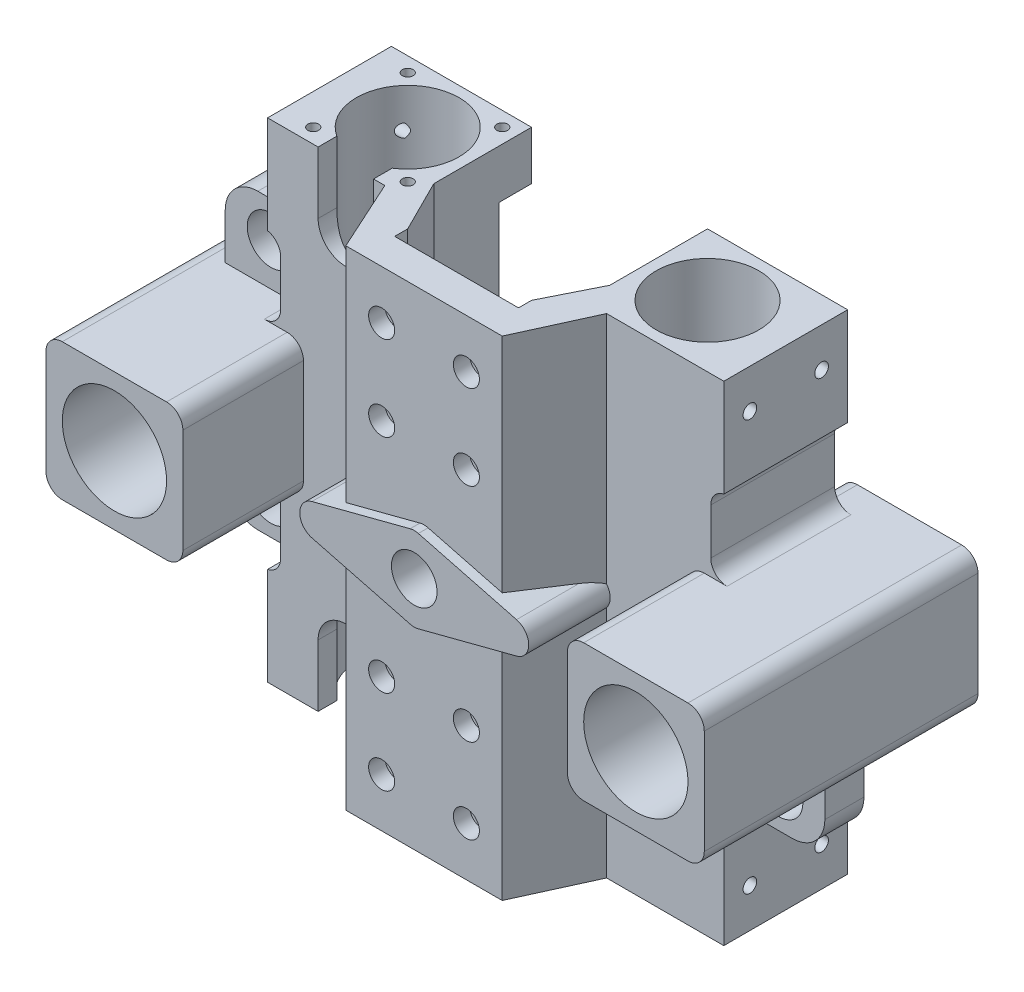
SolidWorks part; units mm, degrees
ref_plane "前视基准面" through (0, 0, 0) normal (0, 0, 1) x (1, 0, 0)
ref_plane "上视基准面" through (0, 0, 0) normal (0, 1, 0) x (1, 0, 0)
ref_plane "右视基准面" through (0, 0, 0) normal (1, 0, 0) x (0, 0, -1)
sketch "草图1" plane through (0, 0, 0) normal (0, 1, 0) x (1, 0, 0)
  line L0 (-70, 0) -> (-27, 0)
  line L1 (-27, 0) -> (-27, -30)
  line L2 (-27, -30) -> (-19, -46)
  line L3 (-19, -46) -> (-19, -50)
  line L4 (-19, -50) -> (19, -50)
  line L5 (0, 0) -> (0, -50.2692) construction
  line L6 (19, -46) -> (19, -50)
  line L7 (27, -30) -> (19, -46)
  line L8 (27, 0) -> (27, -30)
  line L9 (70, 0) -> (27, 0)
  line L10 (-70, 0) -> (-70, -38)
  line L11 (-70, -38) -> (-34.026, -38)
  line L12 (-34.026, -38) -> (-24, -60)
  line L13 (34.026, -38) -> (24, -60)
  line L14 (70, -38) -> (34.026, -38)
  line L15 (-24, -60) -> (24, -60)
  line L16 (70, 0) -> (70, -38)
  point P10 (0, -41.3877)
  dimension "D1" = 140
  dimension "D2" = 54
  dimension "D3" = 4
  dimension "D4" = 38
  dimension "D5" = 50
  dimension "D6" = 30
  dimension "D7" = 60
  dimension "D8" = 38
  dimension "D9" = 48
  dimension "D10" = 49
extrude "凸台-拉伸1" add sketch "草图1" along normal mid plane 150
sketch "草图2" plane through (0, 0, 60) normal (0, 0, 1) x (1, 0, 0)
  line L0 (-50, 0) -> (0, 13)
  line L1 (0, 13) -> (50, 0)
  line L2 (0, 0) -> (50, 0) construction
  line L3 (0, 0) -> (0, 26.231) construction
  line L4 (0, -13) -> (50, 0)
  line L5 (-50, 0) -> (0, -13)
  dimension "D1" = 26
  dimension "D2" = 100
extrude "凸台-拉伸2" add sketch "草图2" along normal blind 3 and the other way up to surface other way up to face at (0, 0, 50)
fillet "圆角1" radius 5 2 edges at (0, -13, 61.5) (0, 13, 61.5)
sketch "草图3" plane through (0, 0, 63) normal (0, 0, 1) x (1, 0, 0)
  circle A0 centre (0, 0) radius 7
  dimension "D1" = 14
extrude "切除-拉伸1" cut sketch "草图3" against normal through all
sketch "草图5" plane through (0, 0, 50) normal (0, 0, -1) x (-1, 0, 0)
  circle A0 centre (0, 0) radius 12.75
  dimension "D1" = 25.5
extrude "切除-拉伸2" cut sketch "草图5" against normal blind 3
hole_wizard "孔1" positions "草图7" profile "草图6" legacy end condition through all
sketch "草图7" plane through (0, 0, 60) normal (0, 0, 1) x (1, 0, 0)
  line L0 (0, 0) -> (0, 65.4079) construction
  line L2 (0, 0) -> (51.5584, 0) construction
  point P0 (-13, 34)
  point P1 (-13, 60)
  point P13 (13, 60)
  point P14 (13, 34)
  point P15 (13, -34)
  point P16 (13, -60)
  point P17 (-13, -60)
  point P18 (-13, -34)
  dimension "D1" = 68
  dimension "D2" = 26
  dimension "D3" = 26
sketch "草图6" plane through (-13, 34, 60) normal (1, 0, 0) x (0, -1, 0)
  line L0 (0, 0) -> (0, 60)
  line L1 (0, 60) -> (2.25, 60)
  line L2 (2.25, 60) -> (2.25, 5)
  line L3 (2.25, 5) -> (4, 5)
  line L4 (4, 5) -> (4, 0)
  line L5 (4, 0) -> (0, 0)
  line L6 (0, 110) -> (0, -10) construction
  dimension "直径" = 4.5
  dimension "深度" = 60
  dimension "柱坑直径" = 8
  dimension "柱坑深度" = 5
sketch "草图8" plane through (0, 75, 0) normal (0, 1, 0) x (1, 0, 0)
  line L0 (0, 0) -> (0, -81.6398) construction
  line L1 (-27, 0) -> (-70, 0) construction
  circle A0 centre (-46, -19) radius 15.75
  circle A1 centre (46, -19) radius 15.75
  dimension "D3" = 31.5
  dimension "D1" = 92
  dimension "D2" = 19
extrude "切除-拉伸3" cut sketch "草图8" against normal through all
sketch "草图10" plane through (0, 0, 38) normal (0, 0, 1) x (1, 0, 0)
  line L0 (-70, 75) -> (-34.026, 75) construction
  line L2 (-54.5, -75) -> (-37.5, -75)
  line L3 (-54.5, -56) -> (-54.5, -75)
  line L4 (0, 0) -> (108.4869, 0) construction
  line L5 (-37.5, -75) -> (-37.5, -56)
  line L8 (0, 0) -> (0, -29.3066) construction
  line L12 (-54.5, 75) -> (-37.5, 75)
  line L13 (-54.5, 56) -> (-54.5, 75)
  line L14 (-37.5, 75) -> (-37.5, 56)
  arc A0 (-37.5, -56) -> (-54.5, -56) centre (-46, -56) ccw
  arc A3 (-37.5, 56) -> (-54.5, 56) centre (-46, 56) cw
  dimension "D3" = 17
  dimension "D1" = 46
  dimension "D2" = 19
extrude "切除-拉伸4" cut sketch "草图10" against normal up to surface (5.7406 mm away)
ref_plane "基准面1" through (0, 0, -9) normal (0, 0, -1) x (-1, 0, 0)
sketch "草图11" plane through (0, 0, -9) normal (0, 0, -1) x (-1, 0, 0)
  line L0 (0, 0) -> (0, 84.6189) construction
  line L1 (101, 21) -> (59, 21)
  line L2 (101, 21) -> (101, -21)
  line L3 (101, -21) -> (59, -21)
  line L4 (59, 21) -> (59, -21)
  line L5 (-59, 21) -> (-59, -21)
  line L6 (-101, -21) -> (-59, -21)
  line L7 (-101, 21) -> (-101, -21)
  line L8 (-101, 21) -> (-59, 21)
  line L9 (0, 0) -> (131.0571, 0) construction
  dimension "D1" = 42
  dimension "D2" = 42
  dimension "D3" = 202
extrude "凸台-拉伸3" add sketch "草图11" against normal blind 84
sketch "草图12" plane through (0, 0, 75) normal (0, 0, 1) x (1, 0, 0)
  line L0 (-80, 21) -> (-80, -21) construction
  line L1 (-101, 21) -> (-59, 21) construction
  line L2 (-59, -21) -> (-101, -21) construction
  line L3 (0, 0) -> (0, 40.2731) construction
  circle A0 centre (-80, 0) radius 16
  circle A1 centre (80, 0) radius 16
  dimension "D1" = 32
extrude "切除-拉伸5" cut sketch "草图12" against normal through all
ref_plane "基准面2" through (0, 0, 17) normal (0, 0, -1) x (-1, 0, 0)
sketch "草图13" plane through (0, 0, 17) normal (0, 0, -1) x (-1, 0, 0)
  line L0 (101, 21) -> (59, 21) construction
  line L1 (92, 21) -> (70, 21)
  line L2 (92, 21) -> (92, 45)
  line L3 (92, 45) -> (70, 45)
  line L4 (70, 21) -> (70, 45)
  line L5 (70, 75) -> (70, 21) construction
  line L6 (0, 0) -> (0, 86.7306) construction
  line L11 (0, 0) -> (135.7522, 0) construction
  line L12 (70, -21) -> (70, -45)
  line L13 (92, -45) -> (70, -45)
  line L14 (92, -21) -> (92, -45)
  line L15 (92, -21) -> (70, -21)
  line L16 (-92, -21) -> (-70, -21)
  line L17 (-92, -21) -> (-92, -45)
  line L18 (-92, -45) -> (-70, -45)
  line L19 (-70, -21) -> (-70, -45)
  dimension "D1" = 90
  dimension "D2" = 184
extrude "凸台-拉伸4" add sketch "草图13" against normal blind 12
sketch "草图14" plane through (0, 0, 38) normal (0, 0, 1) x (1, 0, 0)
  line L0 (-70, 21) -> (-59, 21) construction
  line L1 (-92, 45) -> (-66, 45)
  line L2 (-92, 45) -> (-92, 21)
  line L3 (-92, 21) -> (-66, 21)
  line L4 (-66, 45) -> (-66, 21)
  line L5 (0, 0) -> (0, 62.4764) construction
  line L6 (66, 45) -> (66, 21)
  line L7 (92, 21) -> (66, 21)
  line L8 (92, 45) -> (92, 21)
  line L9 (92, 45) -> (66, 45)
  line L10 (0, 0) -> (-135.212, 0) construction
  line L11 (-66, -45) -> (-66, -21)
  line L12 (-92, -21) -> (-66, -21)
  line L13 (-92, -45) -> (-92, -21)
  line L14 (-92, -45) -> (-66, -45)
  dimension "D1" = 132
extrude "切除-拉伸6" cut sketch "草图14" against normal up to surface (9 mm away) up to face at (-81, 33, 29)
sketch "草图15" plane through (0, 0, 0) normal (0, 0, -1) x (-1, 0, 0)
  line L0 (101, 21) -> (59, 21) construction
  line L1 (92, 45) -> (66, 45)
  line L2 (92, 45) -> (92, 21)
  line L3 (92, 21) -> (66, 21)
  line L4 (66, 45) -> (66, 21)
  line L5 (0, 0) -> (122.7147, 0) construction
  line L6 (0, 0) -> (0, 81.1914) construction
  line L7 (66, -45) -> (66, -21)
  line L8 (92, -21) -> (66, -21)
  line L9 (92, -45) -> (92, -21)
  line L10 (92, -45) -> (66, -45)
  line L11 (-66, 45) -> (-66, 21)
  line L12 (-92, 21) -> (-66, 21)
  line L13 (-92, 45) -> (-92, 21)
  line L14 (-92, 45) -> (-66, 45)
  line L15 (66, 21) -> (66, 45) construction
extrude "切除-拉伸7" cut sketch "草图15" against normal up to surface (17 mm away) up to face at (-81, 33, 17)
fillet "圆角2" radius 5 11 edges at (66, 45, 33.5) (66, 45, 8.5) (66, 21, 8.5) (-66, -45, 8.5) (-66, -21, 8.5) (-66, -45, 33.5) (-66, -21, 33.5) (-66, 45, 33.5) (-66, 21, 33.5) (-66, 21, 8.5) (-66, 45, 8.5)
sketch "草图16" plane through (0, 0, 29) normal (0, 0, 1) x (1, 0, 0)
  line L0 (0, 0) -> (0, 49.2647) construction
  line L1 (0, 0) -> (-125.2782, 0) construction
  circle A0 centre (-78, 34) radius 7.25
  circle A1 centre (-78, -34) radius 7.25
  circle A2 centre (78, -34) radius 7.25
  dimension "D3" = 14.5
  dimension "D1" = 156
  dimension "D2" = 68
extrude "切除-拉伸8" cut sketch "草图16" against normal through all
fillet "圆角3" radius 10 3 edges at (-92, -45, 23) (-92, 45, 23) (92, -45, 23)
hole_wizard "M4x0.7 螺纹孔1" positions "草图18" profile "草图17" tap size "M4x0.7" standard "JIS"
sketch "草图18" plane through (0, 75, 0) normal (0, 1, 0) x (-1, 0, 0)
  line L0 (46, 19) -> (46, -4.6067) construction
  line L2 (46, 19) -> (-13.9014, 19) construction
  point P1 (60.5, 4.5)
  point P14 (60.5, 33.5)
  point P15 (31.5, 33.5)
  point P16 (31.5, 4.5)
  dimension "D1" = 29
  dimension "D2" = 29
sketch "草图17" plane through (-60.5, 75, 4.5) normal (1, 0, 0) x (0, 0, 1)
  line L0 (0, 0) -> (0, 11.0914)
  line L1 (0, 11.0914) -> (1.65, 10.1)
  line L2 (1.65, 10.1) -> (1.65, 0)
  line L5 (1.65, 0) -> (0, 0)
  line L10 (0, 11.0914) -> (-1.65, 10.1) construction
  line L11 (0, -6.35) -> (0, 107.95) construction
  dimension "螺纹孔钻头直径" = 3.3
  dimension "螺纹孔钻头深度" = 10.1
  dimension "导头角度" = 118
cosmetic thread "孔螺蚊线1" parameters "D1"=8, "D2"=4
cosmetic thread "孔螺蚊线2" parameters "D1"=8, "D2"=4
cosmetic thread "孔螺蚊线3" parameters "D1"=8, "D2"=4
cosmetic thread "孔螺蚊线4" parameters "D1"=8, "D2"=4
mirror "镜向1" about plane through (0, 0, 0) normal (0, 1, 0) of "M4x0.7 螺纹孔1"
hole_wizard "M5x0.8 螺纹孔1" positions "草图20" profile "草图19" tap size "M5x0.8" standard "JIS"
sketch "草图20" plane through (-70, 0, 0) normal (-1, 0, 0) x (0, 0, 1)
  line L0 (0, 0) -> (87.5751, 0) construction
  line L2 (19, -75) -> (19, -46.4848) construction
  line L3 (0, -75) -> (38, -75) construction
  point P1 (8, -63)
  point P3 (30, -63)
  point P17 (30, 63)
  point P18 (8, 63)
  dimension "D1" = 22
  dimension "D2" = 12
sketch "草图19" plane through (-70, -63, 8) normal (0, 1, 0) x (0, 0, 1)
  line L0 (0, 0) -> (0, 13.6618)
  line L1 (0, 13.6618) -> (2.1, 12.4)
  line L2 (2.1, 12.4) -> (2.1, 0)
  line L5 (2.1, 0) -> (0, 0)
  line L10 (0, 13.6618) -> (-2.1, 12.4) construction
  line L11 (0, -6.35) -> (0, 107.95) construction
  dimension "螺纹孔钻头直径" = 4.2
  dimension "螺纹孔钻头深度" = 12.4
  dimension "导头角度" = 118
cosmetic thread "孔螺蚊线5" parameters "D1"=10, "D2"=5
cosmetic thread "孔螺蚊线6" parameters "D1"=10, "D2"=5
cosmetic thread "孔螺蚊线7" parameters "D1"=10, "D2"=5
cosmetic thread "孔螺蚊线8" parameters "D1"=10, "D2"=5
mirror "镜向2" about plane through (0, 0, 0) normal (1, 0, 0) of "M5x0.8 螺纹孔1"
sketch "草图21" plane through (0, 0, 38) normal (0, 0, 1) x (1, 0, 0)
  line L1 (59, 21) -> (71, 21) construction
  line L3 (66, 40.101) -> (66, 26) construction
  line L4 (70, 75) -> (70, 45) construction
  line L5 (0, 0) -> (114.8215, 0) construction
  line L6 (66, 21) -> (66, 45)
  line L7 (70, 45) -> (66, 45)
  line L8 (70, 21) -> (70, 45)
  line L9 (70, 21) -> (66, 21)
  dimension "D1" = 24
extrude "切除-拉伸9" cut sketch "草图21" against normal through all
fillet "圆角4" radius 5 2 edges at (66, 21, 19) (66, 45, 19)
sketch "草图22" plane through (0, 0, 0) normal (0, 1, 0) x (1, 0, 0)
  line L0 (-27, 0) -> (-37, 0)
  line L1 (-27, 0) -> (-70, 0) construction
  line L2 (-37, 0) -> (-27, -10)
  line L3 (-27, -30) -> (-27, 0) construction
  line L4 (-27, -10) -> (-27, 0)
  line L5 (0, 0) -> (0, -22.4878) construction
  line L6 (0, -22.4878) -> (0, -16.9787) construction
  line L7 (27, -10) -> (27, 0)
  line L8 (37, 0) -> (27, -10)
  line L9 (27, 0) -> (37, 0)
  dimension "D1" = 10
extrude "切除-拉伸10" cut sketch "草图22" against normal mid plane 120
fillet "圆角5" radius 5 12 edges at (-101, -21, 33) (-59, -21, 56.5) (-59, -21, -4.5) (-59, 21, -4.5) (-59, 21, 56.5) (-101, 21, 33) (101, 21, 33) (59, 21, 56.5) (59, 21, -4.5) (59, -21, -4.5) (59, -21, 56.5) (101, -21, 33)
sketch "草图23" plane through (0, 0, 63) normal (0, 0, 1) x (1, 0, 0)
  line L0 (-50, 0) -> (-24, -6.76)
  line L1 (-24, -6.76) -> (-24, 6.76)
  line L2 (-24, 6.76) -> (-50, 0)
  line L3 (50, 0) -> (24, 6.76)
  line L4 (24, 6.76) -> (24, -6.76)
  line L5 (24, -6.76) -> (50, 0)
extrude "凸台-拉伸5" add sketch "草图23" against normal up to surface (25 mm away) up to face at (-56.7568, 0, 38)
fillet "圆角6" radius 5 2 edges at (50, 0, 50.5) (-50, 0, 50.5)
sketch "草图25" plane through (0, 0, 38) normal (0, 0, 1) x (1, 0, 0)
  line L0 (82, -45) -> (70, -45) construction
  line L1 (70, -21) -> (66, -21)
  line L2 (70, -21) -> (70, -45)
  line L3 (70, -45) -> (66, -45)
  line L4 (66, -21) -> (66, -45)
  line L7 (66, 40.101) -> (66, 26) construction
extrude "切除-拉伸11" cut sketch "草图25" against normal up to surface (9 mm away) up to face at (-85.25, -34, 29)
sketch "草图26" plane through (0, 0, 0) normal (0, 0, -1) x (-1, 0, 0)
  line L0 (-66, -21) -> (-66, -45) construction
  line L1 (-70, -21) -> (-66, -21)
  line L2 (-70, -21) -> (-70, -45)
  line L3 (-70, -45) -> (-66, -45)
  line L4 (-66, -21) -> (-66, -45)
  line L5 (-66, -45) -> (-70, -45) construction
extrude "切除-拉伸12" cut sketch "草图26" against normal up to surface (17 mm away) up to face at (70.75, -34, 17)
fillet "圆角7" radius 5 4 edges at (66, -45, 33.5) (66, -21, 33.5) (66, -45, 8.5) (66, -21, 8.5)
sketch "草图27" plane through (0, 75, 0) normal (0, 1, 0) x (1, 0, 0)
  circle A0 centre (-46, -19) radius 15.75
  circle A1 centre (46, -19) radius 15.75
  circle A2 centre (46, -19) radius 15.75 construction
  arc A3 (-37.5, -32.2594) -> (-54.5, -32.2594) centre (-46, -19) ccw construction
extrude "切除-拉伸13" cut sketch "草图27" against normal through all
